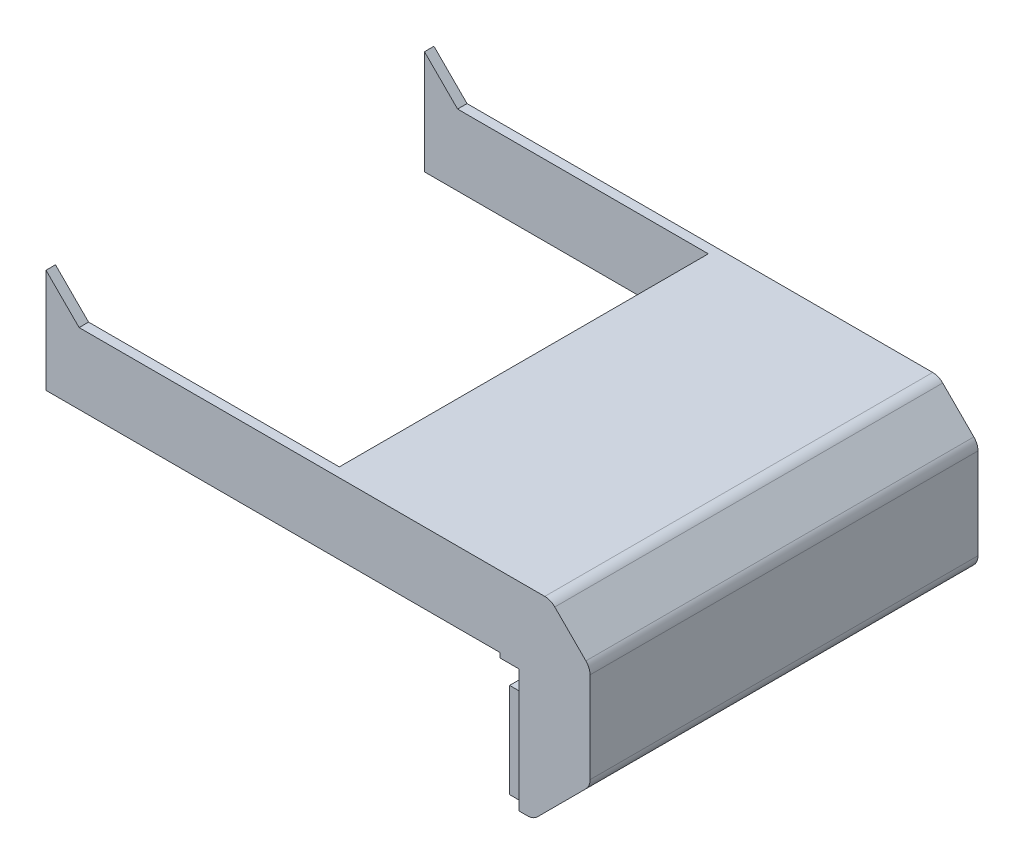
SolidWorks part; units mm, degrees
ref_plane "前视基准面" through (0, 0, 0) normal (0, 0, 1) x (1, 0, 0)
ref_plane "上视基准面" through (0, 0, 0) normal (0, 1, 0) x (1, 0, 0)
ref_plane "右视基准面" through (0, 0, 0) normal (1, 0, 0) x (0, 0, -1)
sketch "草图1" plane through (0, 0, 0) normal (0, 0, 1) x (1, 0, 0)
  line L1 (0, 2) -> (3, 2)
  line L7 (0, 0) -> (3, 0)
  line L14 (-40, 42) -> (-40, 40)
  line L15 (3, 2) -> (13, 12)
  line L16 (3, 0) -> (15, 12)
  line L18 (15, 12) -> (15, 33.6667)
  line L21 (13, 12) -> (13, 33.6667)
  line L22 (13, 33.6667) -> (6.6667, 40)
  line L23 (-40, 40) -> (6.6667, 40)
  line L24 (15, 33.6667) -> (6.6667, 42)
  line L25 (-40, 42) -> (6.6667, 42)
  line L26 (0, 0) -> (0, 2)
extrude "凸台-拉伸1" add sketch "草图1" along normal blind 82
fillet "圆角1" radius 3 8 edges at (3, 0, 41) (15, 12, 41) (3, 2, 41) (6.6667, 42, 41) (15, 33.6667, 41) (6.6667, 40, 41) (13, 33.6667, 41) (13, 12, 41)
sketch "草图2" plane through (0, 0, 0) normal (0, 0, -1) x (-1, 0, 0)
  line L2 (104.8261, 27) -> (98.8261, 27) construction
  line L3 (100, 27) -> (100, 49)
  line L4 (100, 49) -> (93, 42)
  line L5 (93, 42) -> (-5.424, 42)
  line L6 (-7.5453, 41.1213) -> (-14.1213, 34.5453)
  line L7 (-15, 32.424) -> (-15, 13.2426)
  line L8 (-14.1213, 11.1213) -> (-3.8787, 0.8787)
  line L9 (0, 0) -> (-1.7574, 0)
  line L10 (0, 26) -> (4, 26)
  line L11 (4, 26) -> (4, 27)
  line L12 (4, 27) -> (100, 27)
  line L13 (0, 26) -> (0, 0)
  arc A0 (-5.424, 42) -> (-7.5453, 41.1213) centre (-5.424, 39) ccw
  arc A1 (-14.1213, 34.5453) -> (-15, 32.424) centre (-12, 32.424) ccw
  arc A2 (-3.8787, 0.8787) -> (-1.7574, 0) centre (-1.7574, 3) ccw
  arc A3 (-15, 13.2426) -> (-14.1213, 11.1213) centre (-12, 13.2426) ccw
extrude "凸台-拉伸2" add sketch "草图2" against normal blind 2
extrude "凸台-拉伸3" add sketch "草图2<2>" along normal blind 2 from surface starting at face at (3.3445, 21.7333, 82)
sketch "草图2<2>" plane through (0, 0, 0) normal (0, 0, -1) x (-1, 0, 0) same geometry as "草图2"
sketch "草图3" plane through (0, 0, 0) normal (-1, 0, 0) x (0, 0, 1)
  line L0 (1, 1) -> (8, 1)
  line L1 (1, 1) -> (81, 1) construction
  line L2 (8, 1) -> (8, 21)
  line L3 (8, 21) -> (1, 21)
  line L4 (1, 26) -> (1, 3) construction
  line L5 (1, 21) -> (1, 1)
  line L8 (81, 21) -> (81, 1)
  line L9 (74, 21) -> (81, 21)
  line L10 (74, 1) -> (74, 21)
  line L11 (81, 1) -> (74, 1)
extrude "凸台-拉伸4" add sketch "草图3" against normal blind 2
sketch "草图4" plane through (0, 0, 0) normal (-1, 0, 0) x (0, 0, 1)
  line L0 (8, 21) -> (6, 21)
  line L1 (8, 21) -> (2, 21) construction
  line L2 (6, 21) -> (6, 1)
  line L3 (6, 1) -> (8, 1)
  line L4 (8, 1) -> (8, 21)
  line L5 (74, 21) -> (74, 1)
  line L6 (74, 1) -> (76, 1)
  line L7 (76, 1) -> (76, 21)
  line L8 (80, 21) -> (74, 21) construction
  line L9 (76, 21) -> (74, 21)
extrude "凸台-拉伸5" add sketch "草图4" along normal blind 1
sketch "草图5" plane through (-1, 0, 0) normal (-1, 0, 0) x (0, 0, 1)
  line L0 (8, 21) -> (1, 21)
  line L1 (1, 21) -> (1, 1)
  line L2 (1, 1) -> (8, 1)
  line L3 (8, 1) -> (8, 21)
  line L6 (81, 1) -> (74, 1)
  line L7 (74, 1) -> (74, 21)
  line L8 (81, 21) -> (81, 1)
  line L9 (74, 21) -> (81, 21)
extrude "凸台-拉伸6" add sketch "草图5" along normal blind 2
